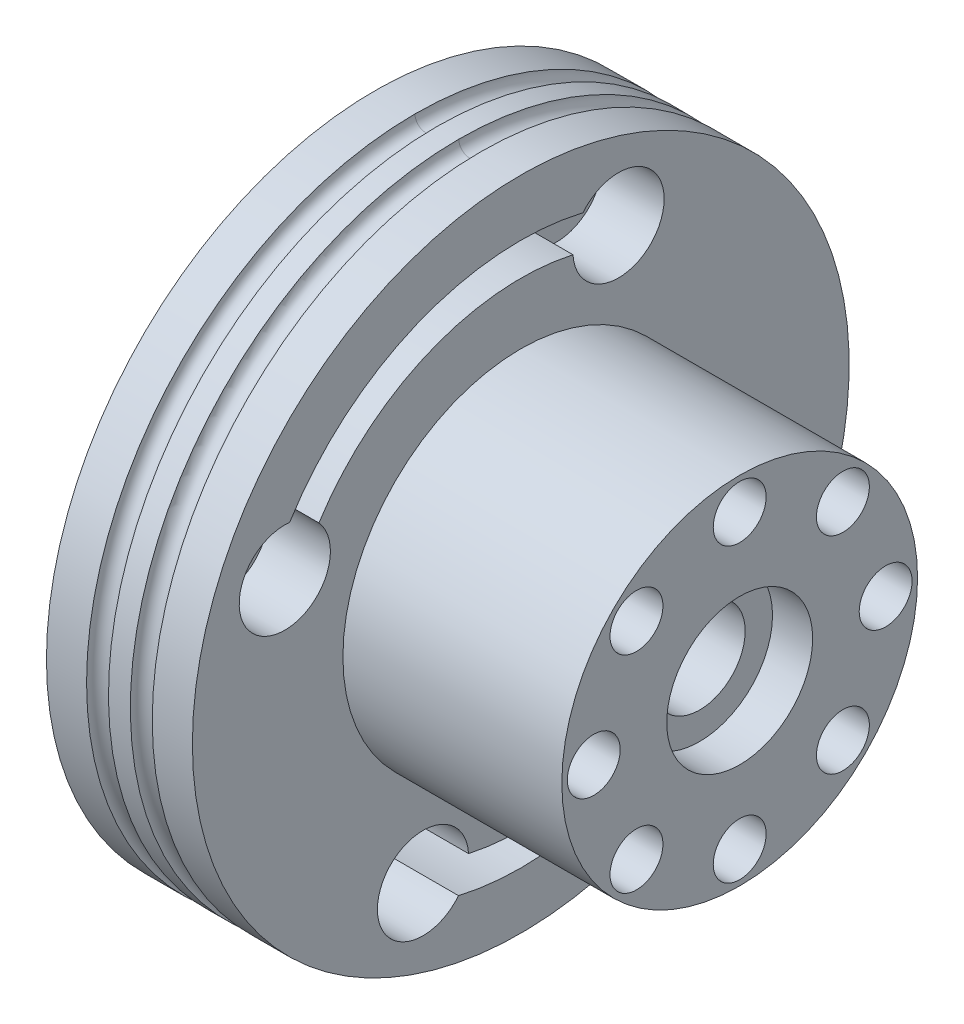
SolidWorks part; units mm, degrees
ref_plane "정면" through (0, 0, 0) normal (0, 0, 1) x (1, 0, 0)
ref_plane "윗면" through (0, 0, 0) normal (0, 1, 0) x (1, 0, 0)
ref_plane "우측면" through (0, 0, 0) normal (1, 0, 0) x (0, 0, -1)
sketch "Sketch1" plane through (0, 0, 0) normal (1, 0, 0) x (0, 0, -1)
  circle A0 centre (0, 0) radius 9.75
  dimension "D1" = 19.5
extrude "Boss-Extrude1" add sketch "Sketch1" along normal blind 20
sketch "Sketch2" plane through (0, 0, 0) normal (-1, 0, 0) x (0, 0, 1)
  circle A0 centre (0, 0) radius 8 construction
  point P3 (0, 8)
  point P6 (5.6569, 5.6569)
  point P7 (8, 0)
  point P8 (5.6569, -5.6569)
  point P9 (0, -8)
  point P10 (-5.6569, -5.6569)
  point P11 (-8, 0)
  point P12 (-5.6569, 5.6569)
  point P13 (0, 0)
  dimension "D1" = 16
  dimension "D2" = 8
sketch "Sketch3" plane through (20, 0, 0) normal (1, 0, 0) x (0, 0, -1)
  circle A0 centre (0, 0) radius 4
  dimension "D1" = 8
extrude "Cut-Extrude1" cut sketch "Sketch3" against normal blind 2.2
sketch "Sketch4" plane through (17.8, 0, 0) normal (1, 0, 0) x (0, 0, -1)
  circle A0 centre (0, 0) radius 2.5
  dimension "D1" = 5
sketch "Sketch5" plane through (0, 0, 0) normal (-1, 0, 0) x (0, 0, 1)
  circle A0 centre (0, 0) radius 18
  dimension "D1" = 36
extrude "Boss-Extrude3" add sketch "Sketch5" against normal blind 8 contours A0
hole_wizard "CBORE for M2.5 Cheese Slotted Head2" positions "3DSketch2" profile "Sketch7" counterbore size "M2.5" standard "KS" end condition through all
sketch3d "3DSketch2"
  point P0 (0, 0, -8)
  point P3 (0, 5.6569, -5.6569)
  point P6 (0, 8, 0)
  point P9 (0, 5.6569, 5.6569)
  point P12 (0, 0, 8)
  point P15 (0, -5.6569, 5.6569)
  point P18 (0, -8, 0)
  point P21 (0, -5.6569, -5.6569)
sketch "Sketch7" plane through (0, 0, -8) normal (0, 1, 0) x (0, 0, 1)
  line L0 (0, 0) -> (0, 20)
  line L1 (0, 20) -> (1.45, 20)
  line L3 (1.45, 20) -> (1.45, 1.8)
  line L4 (1.45, 1.8) -> (2.75, 1.8)
  line L5 (2.75, 1.8) -> (2.75, 0)
  line L7 (2.75, 0) -> (0, 0)
  line L11 (0, -6.35) -> (0, 107.95) construction
  dimension "Thru Hole Dia." = 2.9
  dimension "Thru Hole Depth" = 20
  dimension "C'Bore Dia." = 5.5
  dimension "C'Bore Depth" = 1.8
extrude "Cut-Extrude2" cut sketch "Sketch4" against normal blind 3 contours A0
ref_plane "Plane2" through (0, 0, 18) normal (0, 0, 1) x (1, 0, 0)
ref_plane "Plane4" through (4, 0, 0) normal (1, 0, 0) x (0, 0, -1)
ref_plane "Plane5" through (5.2, 0, 0) normal (1, 0, 0) x (0, 0, -1)
sketch "Sketch9" plane through (5.2, 0, 0) normal (1, 0, 0) x (0, 0, -1)
  circle A0 centre (0, 0) radius 16
ref_axis "Axis1" through (5.2, 17.6, 0) along (0, -1, 0)
sketch "Sketch12" plane through (0, 0, 0) normal (0, 0, 1) x (1, 0, 0)
  line L0 (0, 18) -> (8, 18) construction
  line L1 (5.2, 17.6) -> (5.2, -17.6) construction
  circle A0 centre (5.2, 18) radius 0.6
  point P4 (5.2, 18)
sweep "Cut-Sweep1" cut profiles "Sketch12" path "Sketch9"
ref_plane "Plane9" through (4.6, 0, 0) normal (1, 0, 0) x (0, 0, -1)
mirror "Mirror1" about plane through (4, 0, 0) normal (1, 0, 0) of "Cut-Sweep1"
ref_plane "Plane10" through (2.2, 0, 0) normal (1, 0, 0) x (0, 0, -1)
sketch "Sketch15" plane through (8, 0, 0) normal (1, 0, 0) x (0, 0, -1)
  line L0 (0, 0) -> (0, 8) construction
  line L1 (0, 0) -> (5.6569, 5.6569) construction
  line L2 (0, 0) -> (5.3576, 12.9343) construction
  line L4 (5.3576, 12.9343) -> (2.8525, 13.972) construction
  circle A0 centre (0, 0) radius 14 construction
  arc A1 (2.8621, 12.7835) -> (3.4119, 14.5041) centre (5.3576, 12.9343) ccw
  circle A2 centre (12.9343, -5.3576) radius 2.5 construction
  circle A3 centre (-5.3576, -12.9343) radius 2.5 construction
  arc A4 (-12.6685, 7.8434) -> (-11.0631, 7.0155) centre (-12.9343, 5.3576) ccw
  arc A5 (-11.7752, 7.5726) -> (5.3576, 12.9343) centre (0, 0) cw construction
  arc A6 (-11.7752, 7.5726) -> (5.3576, 12.9343) centre (0, 0) cw construction
  arc A7 (3.4119, 14.5041) -> (-12.6685, 7.8434) centre (0, 0) ccw
  arc A8 (2.8621, 12.7835) -> (-11.0631, 7.0155) centre (0, 0) ccw
  point P9 (1.7584, 17.9139)
  point P11 (-5.3576, 12.9343)
  point P18 (0, 0)
  point P24 (3.4119, 17.6737)
  point P26 (3.4119, 17.6737)
  dimension "D1" = 22.5
  dimension "D2" = 28
  dimension "D3" = 4
  dimension "D4" = 5
extrude "Cut-Extrude3" cut sketch "Sketch15" against normal up to surface (3.4 mm away) up to plane "Plane9"
sketch "Sketch16" plane through (4.6, 0, 0) normal (1, 0, 0) x (0, 0, -1)
  point P0 (5.3576, 12.9343)
  point P1 (-12.9343, 5.3576)
sketch "Sketch17" plane through (8, 0, 0) normal (1, 0, 0) x (0, 0, -1)
  line L0 (0, 0) -> (0, -8) construction
  line L1 (0, 0) -> (-5.6569, -5.6569) construction
  line L2 (0, 0) -> (-5.3576, -12.9343) construction
  circle A0 centre (0, 0) radius 14 construction
  arc A1 (-2.8621, -12.7835) -> (-3.4119, -14.5041) centre (-5.3576, -12.9343) ccw
  circle A2 centre (-12.9343, 5.3576) radius 2.5 construction
  circle A3 centre (5.3576, 12.9343) radius 2.5 construction
  arc A4 (12.6685, -7.8434) -> (11.0631, -7.0155) centre (12.9343, -5.3576) ccw
  arc A5 (12.9343, -5.3576) -> (-5.3576, -12.9343) centre (0, 0) cw construction
  arc A6 (-3.4119, -14.5041) -> (12.6685, -7.8434) centre (0, 0) ccw
  arc A7 (-2.8621, -12.7835) -> (11.0631, -7.0155) centre (0, 0) ccw
  point P11 (5.3576, -12.9343)
  point P19 (0, 0)
  dimension "D1" = 22.5
  dimension "D2" = 4
ref_plane "Plane6" through (2.8, 0, 0) normal (1, 0, 0) x (0, 0, -1)
extrude "Cut-Extrude4" cut sketch "Sketch17" against normal up to surface (5.8 mm away) up to plane "Plane10"
hole_wizard "M2 Tapped Hole2" positions "3DSketch7" profile "Sketch21" tap size "M2" standard "KS" end condition through all
sketch3d "3DSketch7"
  point P0 (4.6, 5.3576, 12.9343)
  point P3 (4.6, 12.9343, -5.3576)
sketch "Sketch21" plane through (4.6, 5.3576, 12.9343) normal (0, 1, 0) x (0, 0, -1)
  line L0 (0, 0) -> (0, 4.6)
  line L1 (0, 4.6) -> (0.8, 4.6)
  line L2 (0.8, 4.6) -> (0.8, 0)
  line L5 (0.8, 0) -> (0, 0)
  line L11 (0, -6.35) -> (0, 107.95) construction
  dimension "Thru Tap Drill Dia." = 1.6
  dimension "Thru Tap Drill Depth" = 4.6
cosmetic thread "Hole Thread1" parameters "D2"=2
cosmetic thread "Hole Thread2" parameters "D2"=2
sketch "Sketch22" plane through (2.2, 0, 0) normal (1, 0, 0) x (0, 0, -1)
  point P0 (-5.3576, -12.9343)
  point P1 (12.9343, -5.3576)
hole_wizard "M2 Tapped Hole3" positions "3DSketch8" profile "Sketch23" tap size "M2" standard "KS" end condition through all
sketch3d "3DSketch8"
  point P0 (2.2, -12.9343, 5.3576)
  point P3 (2.2, -5.3576, -12.9343)
sketch "Sketch23" plane through (2.2, -12.9343, 5.3576) normal (0, 1, 0) x (0, 0, -1)
  line L0 (0, 0) -> (0, 2.2)
  line L1 (0, 2.2) -> (0.8, 2.2)
  line L2 (0.8, 2.2) -> (0.8, 0)
  line L5 (0.8, 0) -> (0, 0)
  line L11 (0, -6.35) -> (0, 107.95) construction
  dimension "Thru Tap Drill Dia." = 1.6
  dimension "Thru Tap Drill Depth" = 2.2
cosmetic thread "Hole Thread3" parameters "D2"=2
cosmetic thread "Hole Thread4" parameters "D2"=2
sketch "Sketch26" plane through (5.2, 0, 0) normal (1, 0, 0) x (0, 0, -1)
  line L0 (5.3576, 12.9343) -> (0, 0) construction
  line L1 (5.3576, 12.9343) -> (15.8101, 8.6047) construction
  circle A1 centre (0, 0) radius 18 construction
  arc A2 (5.3576, 12.9343) -> (15.8101, 8.6047) centre (8.419, 5.5433) cw
ref_plane "Plane11" through (5.2, 8.6047, -15.8101) normal (0, -0.9239, -0.3827) x (-1, 0, 0)
sketch "Sketch27" plane through (5.2, 8.6047, -15.8101) normal (0, -0.9239, -0.3827) x (-1, 0, 0)
  circle A0 centre (0, 0) radius 0.6
sweep "Cut-Sweep2" cut profiles "Sketch27" path "Sketch26"
sketch "Sketch29" plane through (2.8, 0, 0) normal (1, 0, 0) x (0, 0, -1)
  line L0 (0, 0) -> (12.9343, -5.3576) construction
  line L1 (12.9343, -5.3576) -> (17.2639, 5.0949) construction
  circle A0 centre (0, 0) radius 18 construction
  arc A1 (17.2639, 5.0949) -> (12.9343, -5.3576) centre (9.8728, 2.0335) cw
ref_plane "Plane13" through (2.8, 5.0949, -17.2639) normal (0, -0.9239, -0.3827) x (-1, 0, 0)
sketch "Sketch31" plane through (2.8, 5.0949, -17.2639) normal (0, -0.9239, -0.3827) x (-1, 0, 0)
  circle A0 centre (0, 0) radius 0.6
sweep "Cut-Sweep3" cut profiles "Sketch31" path "Sketch29"
